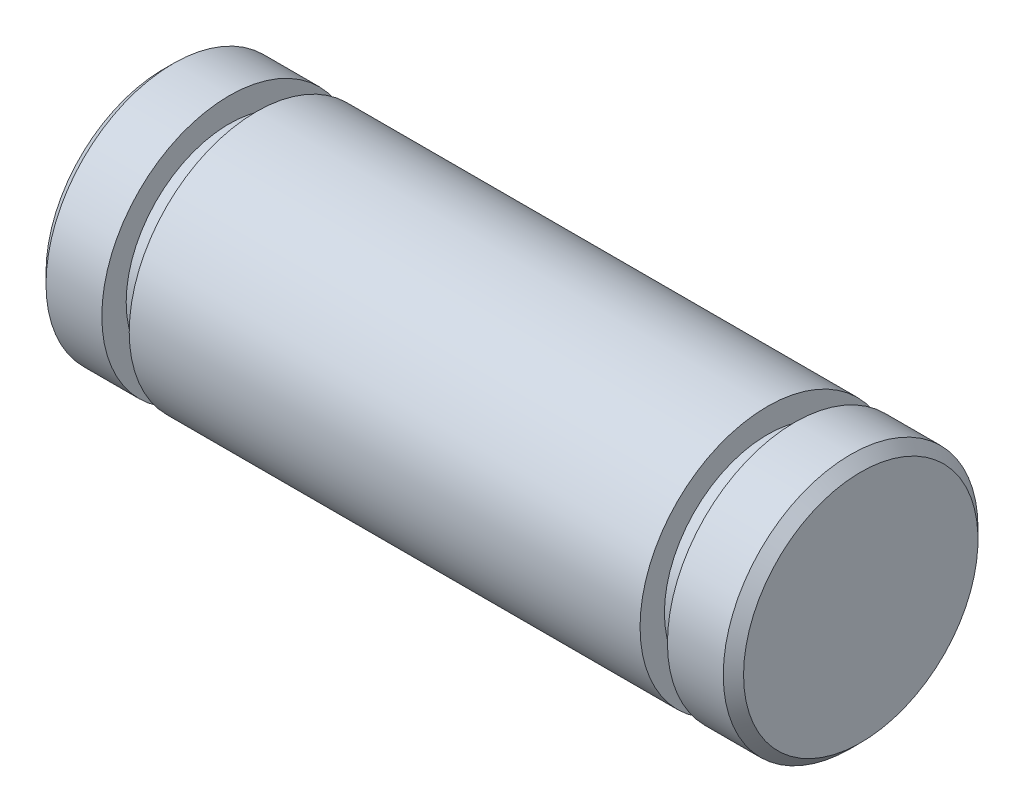
SolidWorks part; units mm, degrees
material "AISI 1045 Steel, cold drawn"
ref_plane "Front Plane" through (0, 0, 0) normal (0, 0, 1) x (1, 0, 0)
ref_plane "Top Plane" through (0, 0, 0) normal (0, 1, 0) x (1, 0, 0)
ref_plane "Right Plane" through (0, 0, 0) normal (1, 0, 0) x (0, 0, -1)
sketch "Sketch1" plane through (0, 0, 0) normal (0, 0, 1) x (1, 0, 0)
  line L0 (-13.0937, 0) -> (-13.0937, 4.4006)
  line L1 (-13.0937, 4.4006) -> (-12.7127, 4.7816)
  line L2 (-12.7127, 4.7816) -> (-10.6172, 4.7816)
  line L3 (-10.6172, 4.7816) -> (-10.6172, 3.8672)
  line L4 (-10.6172, 3.8672) -> (-9.5885, 3.8672)
  line L5 (-9.5885, 3.8672) -> (-9.5885, 4.7816)
  line L6 (-9.5885, 4.7816) -> (9.5885, 4.7816)
  line L7 (9.5885, 4.7816) -> (9.5885, 3.8672)
  line L8 (9.5885, 3.8672) -> (10.6172, 3.8672)
  line L9 (10.6172, 3.8672) -> (10.6172, 4.7816)
  line L10 (10.6172, 4.7816) -> (12.7127, 4.7816)
  line L11 (12.7127, 4.7816) -> (13.0937, 4.4006)
  line L12 (13.0937, 4.4006) -> (13.0937, 0)
  line L13 (13.0937, 0) -> (-13.0937, 0)
  line L14 (13.0937, 0) -> (-13.0937, 0) construction
revolve "Revolve1" add sketch "Sketch1" angle 360 about L14 reverse direction yes
ref_plane "Plane1" through (10.1029, 0, 0) normal (1, 0, 0) x (0, 0, -1)
ref_plane "Plane2" through (-10.1029, 0, 0) normal (1, 0, 0) x (0, 0, -1)
ref_plane "p1 XY" through (0, 0, 0) normal (1, 0, 0) x (0, 0, -1)
ref_plane "p1 XZ" through (0, 0, 0) normal (0, -1, 0) x (-1, 0, 0)
ref_plane "p1 YZ" through (0, 0, 4.7816) normal (0, 0, -1) x (-1, 0, 0)
ref_axis "p1 X" through (0, 0, 80.9) along (0, 0, -1)
ref_axis "p1 Y" through (0, -50, 4.7816) along (0, 1, 0)
ref_axis "p1 Z" through (80.9, 0, 4.7816) along (-1, 0, 0)
sketch3d "p1"
  point P0 (0, 0, 4.7816)
ref_plane "p2 XY" through (0, 0, 0) normal (1, 0, 0) x (0, 0, -1)
ref_plane "p2 XZ" through (0, 0, 0) normal (0, -1, 0) x (-1, 0, 0)
ref_plane "p2 YZ" through (0, 0, -4.7816) normal (0, 0, -1) x (-1, 0, 0)
ref_axis "p2 X" through (0, 0, 80.9) along (0, 0, -1)
ref_axis "p2 Y" through (0, -50, -4.7816) along (0, 1, 0)
ref_axis "p2 Z" through (80.9, 0, -4.7816) along (-1, 0, 0)
sketch3d "p2"
  point P0 (0, 0, -4.7816)
ref_plane "pin XY" through (0, 0, 0) normal (1, 0, 0) x (0, 0, -1)
ref_plane "pin XZ" through (0, 0, 0) normal (0, -1, 0) x (-1, 0, 0)
ref_plane "pin YZ" through (0, 0, 0) normal (0, 0, -1) x (-1, 0, 0)
ref_axis "pin X" through (0, 0, 80.9) along (0, 0, -1)
ref_axis "pin Y" through (0, -50, 0) along (0, 1, 0)
ref_axis "pin Z" through (80.9, 0, 0) along (-1, 0, 0)
sketch3d "pin"
  point P0 (0, 0, 0)
ref_plane "rr1 XY" through (10.1029, 0, 0) normal (1, 0, 0) x (0, 0, -1)
ref_plane "rr1 XZ" through (0, 0, 0) normal (0, -1, 0) x (-1, 0, 0)
ref_plane "rr1 YZ" through (0, 0, 0) normal (0, 0, -1) x (-1, 0, 0)
ref_axis "rr1 X" through (10.1029, 0, 80.9) along (0, 0, -1)
ref_axis "rr1 Y" through (10.1029, -50, 0) along (0, 1, 0)
ref_axis "rr1 Z" through (80.9, 0, 0) along (-1, 0, 0)
sketch3d "rr1"
  point P0 (10.1029, 0, 0)
ref_plane "rr2 XY" through (-10.1029, 0, 0) normal (1, 0, 0) x (0, 0, -1)
ref_plane "rr2 XZ" through (0, 0, 0) normal (0, -1, 0) x (-1, 0, 0)
ref_plane "rr2 YZ" through (0, 0, 0) normal (0, 0, -1) x (-1, 0, 0)
ref_axis "rr2 X" through (-10.1029, 0, 80.9) along (0, 0, -1)
ref_axis "rr2 Y" through (-10.1029, -50, 0) along (0, 1, 0)
ref_axis "rr2 Z" through (80.9, 0, 0) along (-1, 0, 0)
sketch3d "rr2"
  point P0 (-10.1029, 0, 0)
ref_plane "w21 XY" through (0, 0, 0) normal (0, 1, 0) x (1, 0, 0)
ref_plane "w21 XZ" through (0, 0, 0) normal (0, 0, 1) x (1, 0, 0)
ref_plane "w21 YZ" through (13.0937, 0, 0) normal (1, 0, 0) x (0, 0, -1)
ref_axis "w21 X" through (-80.9, 0, 0) along (1, 0, 0)
ref_axis "w21 Y" through (13.0937, 0, 50) along (0, 0, -1)
ref_axis "w21 Z" through (13.0937, 50, 0) along (0, -1, 0)
sketch3d "w21"
  point P0 (13.0937, 0, 0)
ref_plane "w22 XY" through (0, 0, 0) normal (0, 1, 0) x (1, 0, 0)
ref_plane "w22 XZ" through (0, 0, 0) normal (0, 0, 1) x (1, 0, 0)
ref_plane "w22 YZ" through (-13.0937, 0, 0) normal (1, 0, 0) x (0, 0, -1)
ref_axis "w22 X" through (-80.9, 0, 0) along (1, 0, 0)
ref_axis "w22 Y" through (-13.0937, 0, 50) along (0, 0, -1)
ref_axis "w22 Z" through (-13.0937, 50, 0) along (0, -1, 0)
sketch3d "w22"
  point P0 (-13.0937, 0, 0)
